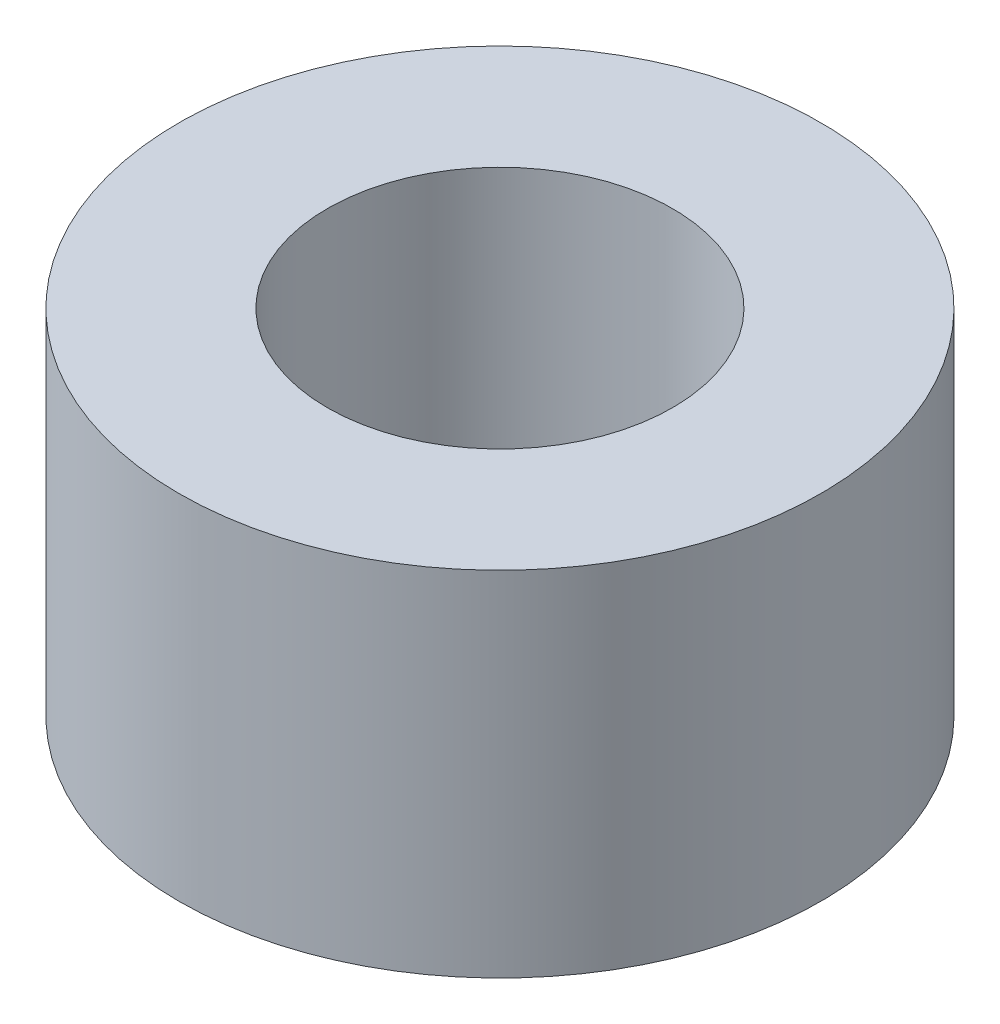
SolidWorks part; units mm, degrees
ref_plane "Front Plane" through (0, 0, 0) normal (0, 0, 1) x (1, 0, 0)
ref_plane "Top Plane" through (0, 0, 0) normal (0, 1, 0) x (1, 0, 0)
ref_plane "Right Plane" through (0, 0, 0) normal (1, 0, 0) x (0, 0, -1)
ref_plane "Mid Plane" through (0, 10.1625, 0) normal (0, 1, 0) x (1, 0, 0)
sketch "Spacer Sketch" plane through (0, 10.1625, 0) normal (0, 1, 0) x (1, 0, 0)
  circle A0 centre (0, -15.04) radius 4
  circle A1 centre (0, -15.04) radius 2.15
extrude "Spacer" add sketch "Spacer Sketch" along normal mid plane 4.4
ref_axis "Engine Axis" through (4.4, 0, 0) along (-1, 0, 0)
